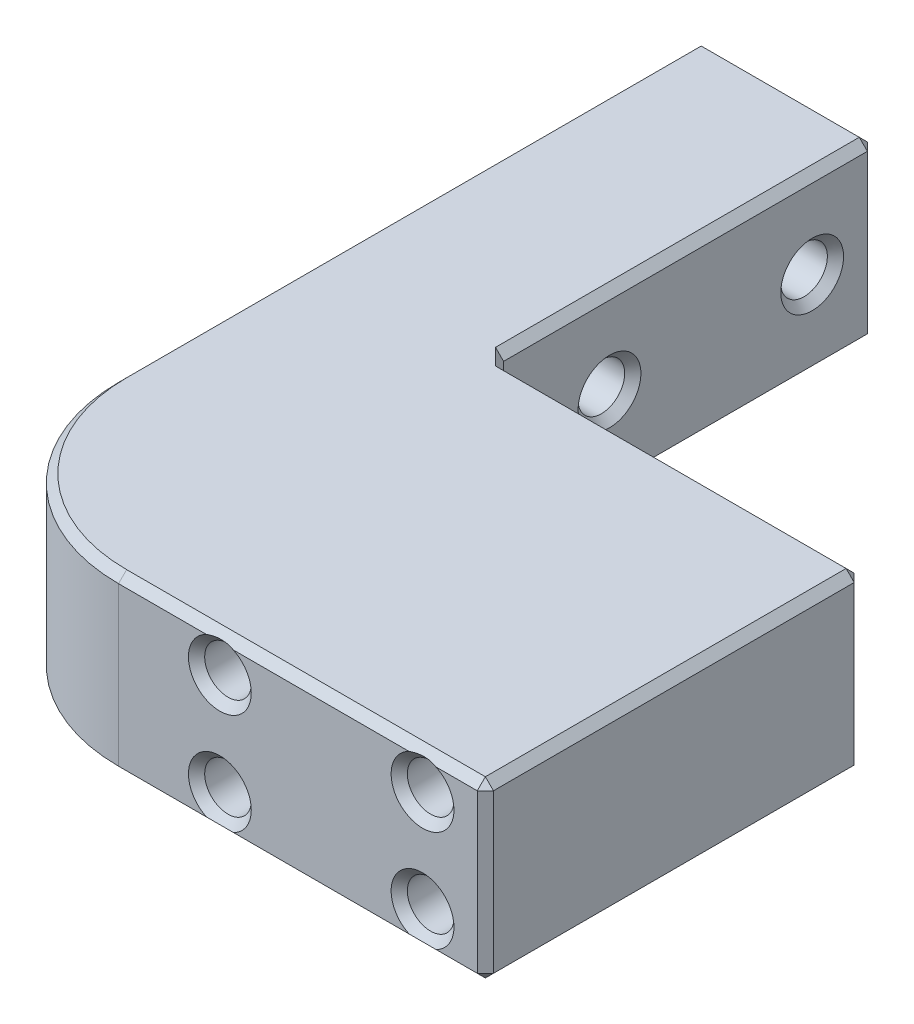
SolidWorks part; units mm, degrees
ref_plane "Front Plane" through (0, 0, 0) normal (0, 0, 1) x (1, 0, 0)
ref_plane "Top Plane" through (0, 0, 0) normal (0, 1, 0) x (1, 0, 0)
ref_plane "Right Plane" through (0, 0, 0) normal (1, 0, 0) x (0, 0, -1)
sketch "Sketch1" plane through (0, 0, 0) normal (0, 1, 0) x (1, 0, 0)
  line L0 (0, 21.844) -> (0, 94.869)
  line L1 (0, 94.869) -> (21.844, 94.869)
  line L2 (21.844, 94.869) -> (21.844, 47.244)
  line L3 (21.844, 47.244) -> (67.818, 47.244)
  line L4 (67.818, 47.244) -> (67.818, 0)
  line L5 (67.818, 0) -> (21.844, 0)
  arc A0 (21.844, 0) -> (0, 21.844) centre (21.844, 21.844) cw
  point P9 (0, 0)
  dimension "D5" = 21.844
  dimension "D1" = 21.844
  dimension "D2" = 47.244
  dimension "D3" = 47.625
  dimension "D4" = 67.818
extrude "Boss-Extrude1" add sketch "Sketch1" along normal blind 21.844
sketch "Sketch2" plane through (21.844, 0, 0) normal (1, 0, 0) x (0, 0, -1)
  line L0 (47.244, 10.922) -> (94.869, 10.922) construction
  line L1 (47.244, 21.844) -> (47.244, 0) construction
  line L2 (94.869, 21.844) -> (94.869, 0) construction
  circle A0 centre (61.5315, 10.922) radius 2.921
  circle A1 centre (86.9315, 10.922) radius 2.921
  dimension "D1" = 5.842
  dimension "D2" = 14.2875
  dimension "D3" = 25.4
extrude "Cut-Extrude1" cut sketch "Sketch2" against normal through all
sketch "Sketch3" plane through (0, 0, -47.244) normal (0, 0, -1) x (-1, 0, 0)
  line L0 (-21.844, 10.922) -> (-67.818, 10.922) construction
  line L1 (-21.844, 21.844) -> (-21.844, 0) construction
  line L2 (-67.818, 21.844) -> (-67.818, 0) construction
  circle A0 centre (-34.544, 17.272) radius 2.921
  circle A1 centre (-59.944, 17.272) radius 2.921
  circle A2 centre (-34.544, 4.572) radius 2.921
  circle A3 centre (-59.944, 4.572) radius 2.921
  dimension "D1" = 5.842
  dimension "D2" = 12.7
  dimension "D3" = 25.4
  dimension "D4" = 6.35
extrude "Cut-Extrude2" cut sketch "Sketch3" against normal through all
chamfer "Chamfer1" distance 1.016 angle 45 31 edges at (62.865, 4.572, -47.244) (62.865, 4.572, 0) (37.465, 4.572, -47.244) (37.465, 4.572, 0) (57.023, 17.272, -47.244) (57.023, 17.272, 0) (31.623, 17.272, -47.244) (31.623, 17.272, 0) (21.844, 10.922, -89.8525) (0, 10.922, -89.8525) (21.844, 10.922, -64.4525) (0, 10.922, -64.4525) (10.922, 0, -94.869) (0, 0, -58.3565) (6.398, 0, -6.398) (44.831, 0, 0) (67.818, 0, -23.622) (44.831, 0, -47.244) (21.844, 0, -71.0565) (10.922, 21.844, -94.869) (21.844, 10.922, -94.869) (21.844, 21.844, -71.0565) (21.844, 10.922, -47.244) (44.831, 21.844, -47.244) (67.818, 10.922, -47.244) (67.818, 21.844, -23.622) (67.818, 10.922, 0) (44.831, 21.844, 0) (6.398, 21.844, -6.398) (0, 21.844, -58.3565) (0, 10.922, -94.869)
